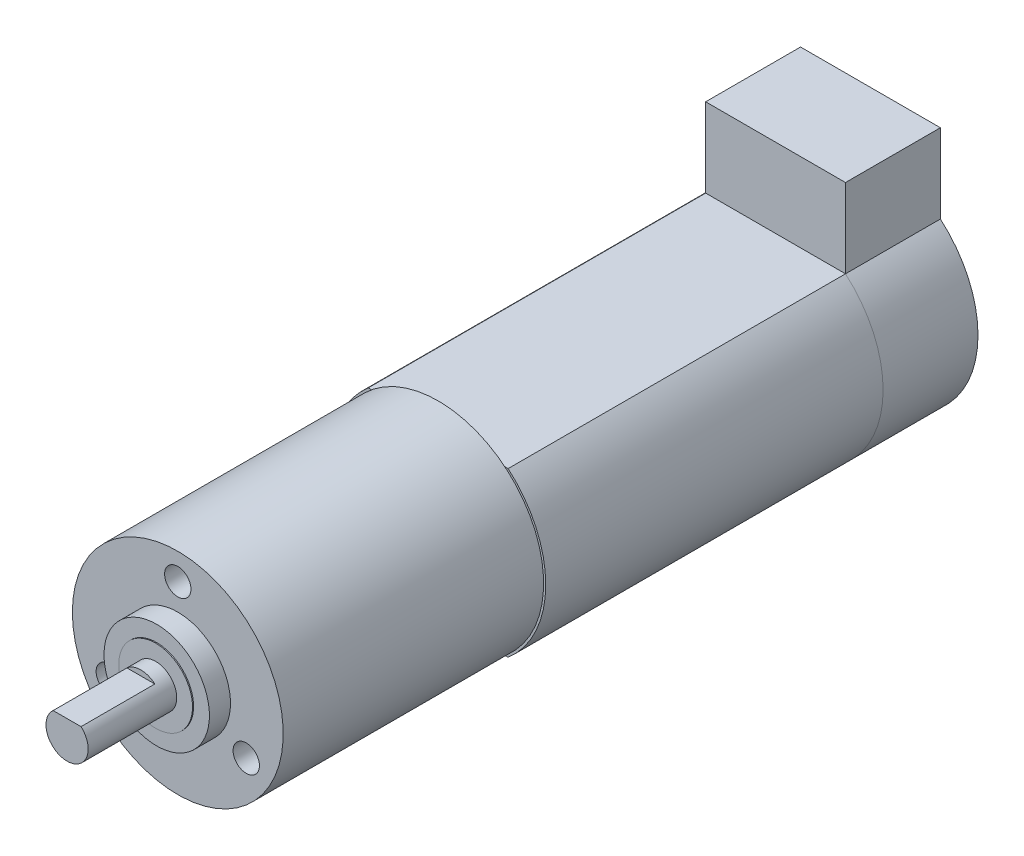
SolidWorks part; units mm, degrees
ref_plane "Front Plane" through (0, 0, 0) normal (0, 0, 1) x (1, 0, 0)
ref_plane "Top Plane" through (0, 0, 0) normal (0, 1, 0) x (1, 0, 0)
ref_plane "Right Plane" through (0, 0, 0) normal (1, 0, 0) x (0, 0, -1)
sketch "Sketch1" plane through (0, 0, 0) normal (0, 0, 1) x (1, 0, 0)
  line L0 (-1.3229, 1.5) -> (1.3229, 1.5)
  arc A0 (-1.3229, 1.5) -> (1.3229, 1.5) centre (0, 0) ccw
  dimension "D1" = 2
  dimension "D2" = 1.5
extrude "Boss-Extrude1" add sketch "Sketch1" against normal blind 7
sketch "Sketch2" plane through (0, 0, -7) normal (0, 0, -1) x (-1, 0, 0)
  circle A0 centre (0, 0) radius 2
extrude "Boss-Extrude2" add sketch "Sketch2" along normal blind 1.4
sketch "Sketch3" plane through (0, 0, -8.4) normal (0, 0, -1) x (-1, 0, 0)
  circle A0 centre (0, 0) radius 3.5
  dimension "D1" = 7
extrude "Boss-Extrude3" add sketch "Sketch3" along normal blind 0.1
sketch "Sketch4" plane through (0, 0, -8.5) normal (0, 0, -1) x (-1, 0, 0)
  circle A0 centre (0, 0) radius 5
  dimension "D1" = 10
extrude "Boss-Extrude4" add sketch "Sketch4" along normal blind 2 separate body
sketch "Sketch5" plane through (0, 0, -10.5) normal (0, 0, -1) x (-1, 0, 0)
  circle A0 centre (0, 0) radius 10
  dimension "D1" = 20
extrude "Boss-Extrude5" add sketch "Sketch5" along normal blind 24.7
sketch "Sketch6" plane through (0, 0, -10.5) normal (0, 0, 1) x (1, 0, 0)
  line L0 (0, 0) -> (0, 7.5) construction
  line L1 (6.4952, -3.75) -> (0, 0) construction
  line L2 (0, 0) -> (-6.4952, -3.75) construction
  line L3 (0, 0) -> (0, 10) construction
  circle A0 centre (0, 0) radius 7.5 construction
  circle A1 centre (0, 7.5) radius 1.25
  circle A2 centre (6.4952, -3.75) radius 1.25
  circle A3 centre (-6.4952, -3.75) radius 1.25
  circle A4 centre (0, 0) radius 10 construction
  dimension "D1" = 15
  dimension "D5" = 2.5
  dimension "D2" = 120
  dimension "D3" = 120
  dimension "D4" = 0
extrude "Screw Holes" cut sketch "Sketch6" against normal blind 5
sketch "Sketch10" plane through (0, 0, -35.2) normal (0, 0, -1) x (-1, 0, 0)
  line L0 (-6.6316, 7.75) -> (6.6316, 7.75)
  line L1 (-6.6316, -7.75) -> (6.6316, -7.75)
  arc A0 (-6.6316, 7.75) -> (-6.6316, -7.75) centre (0, 0) ccw
  arc A1 (6.6316, -7.75) -> (6.6316, 7.75) centre (0, 0) ccw
  dimension "D1" = 10.2
  dimension "D2" = 15.5
extrude "Motor" add sketch "Sketch10" along normal blind 32 separate body
sketch "Sketch11" plane through (0, 0, -67.2) normal (0, 0, -1) x (-1, 0, 0)
  line L1 (-6.6316, -7.75) -> (6.6316, -7.75)
  line L4 (-6.6316, 7.75) -> (-6.6316, 15.25)
  line L5 (-6.6316, 15.25) -> (6.6316, 15.25)
  line L6 (6.6316, 7.75) -> (6.6316, 15.25)
  arc A0 (6.6316, -7.75) -> (6.6316, 7.75) centre (0, 0) ccw
  arc A1 (-6.6316, 7.75) -> (-6.6316, -7.75) centre (0, 0) ccw
  dimension "D1" = 23
extrude "Encoder" add sketch "Sketch11" along normal blind 9 separate body
